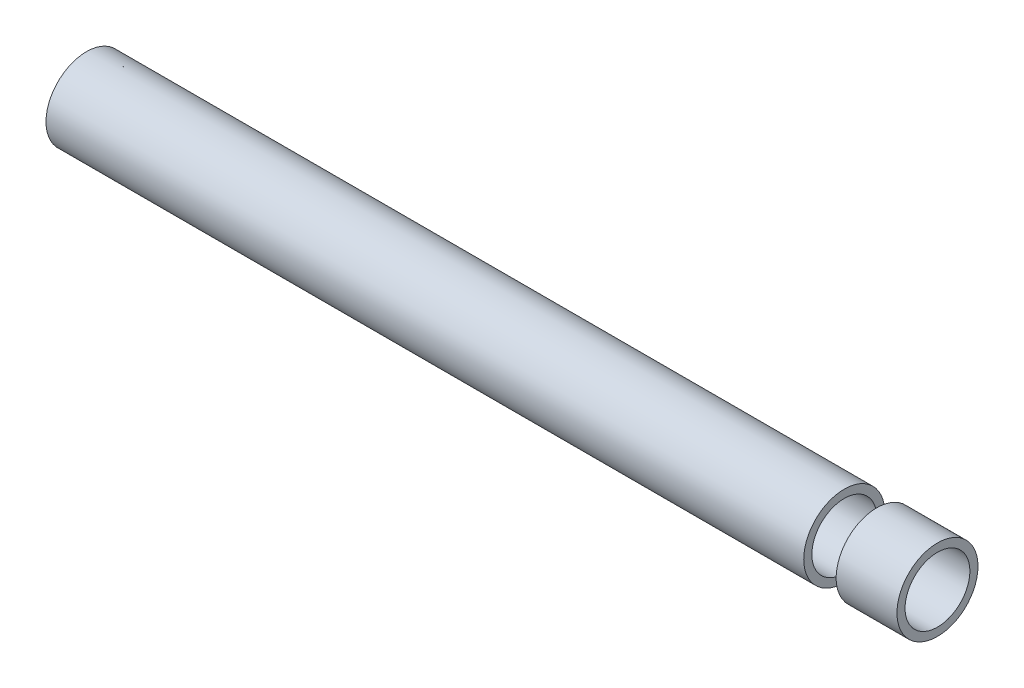
SolidWorks part; units mm, degrees
material "PC High Viscosity"
ref_plane "Front Plane" through (0, 0, 0) normal (0, 0, 1) x (1, 0, 0)
ref_plane "Top Plane" through (0, 0, 0) normal (0, 1, 0) x (1, 0, 0)
ref_plane "Right Plane" through (0, 0, 0) normal (1, 0, 0) x (0, 0, -1)
sketch "Sketch1" plane through (0, 0, 0) normal (1, 0, 0) x (0, 0, -1)
  circle A0 centre (0, 0) radius 15.875
  dimension "D1" = 31.75
extrude "Extrude-Thin1" add sketch "Sketch1" along normal mid plane 333.3432 thin thin type one direction reverse wall 3.175
sketch "Sketch2" plane through (0, 0, 0) normal (0, 0, 1) x (1, 0, 0)
  line L0 (166.6716, -15.875) -> (166.6716, 15.875) construction
  line L1 (130.1591, -15.875) -> (142.8591, -15.875)
  line L2 (130.1591, -15.875) -> (130.1591, 15.875)
  line L3 (130.1591, 15.875) -> (142.8591, 15.875)
  line L4 (142.8591, -15.875) -> (142.8591, 15.875)
  line L5 (-166.6716, -15.875) -> (166.6716, -15.875) construction
  line L6 (166.6716, 15.875) -> (-166.6716, 15.875) construction
  point P6 (142.8591, -15.875)
  point P9 (130.1591, 15.875)
  dimension "D1" = 12.7
  dimension "D2" = 23.8125
extrude "Cut-Extrude1" cut sketch "Sketch2" against normal through all both and the other way through all
equation "\"D2@Sketch2\"=1+0.10718504-0.16968504"
